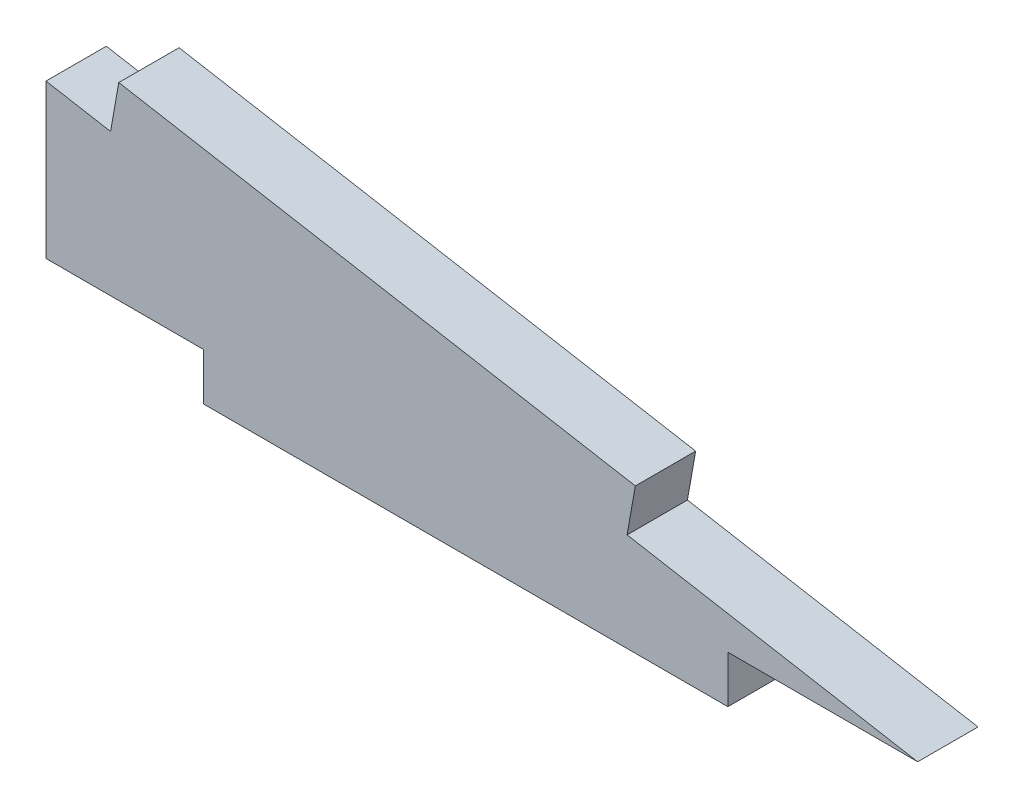
SolidWorks part; units mm, degrees
ref_plane "前视基准面" through (0, 0, 0) normal (0, 0, 1) x (1, 0, 0)
ref_plane "上视基准面" through (0, 0, 0) normal (0, 1, 0) x (1, 0, 0)
ref_plane "右视基准面" through (0, 0, 0) normal (1, 0, 0) x (0, 0, -1)
other "Configuration Table"
sketch "草图1" plane through (0, 0, 0) normal (0, 0, 1) x (1, 0, 0)
  line L2 (-22.3823, 3.7158) -> (-22.3823, 7.3158)
  line L3 (17.6177, 3.7158) -> (17.6177, 7.3158)
  line L4 (-22.3823, 7.3158) -> (-34.3823, 7.3158)
  line L5 (17.6177, 7.3158) -> (24.855, 7.3158)
  line L6 (-34.3823, 7.3158) -> (-34.3823, 19.037)
  line L7 (-34.3823, 19.037) -> (-29.4582, 18.1688)
  line L10 (-29.4582, 18.1688) -> (-28.8331, 21.7141)
  line L11 (-28.8331, 21.7141) -> (10.5592, 14.7681)
  line L12 (10.5592, 14.7681) -> (9.9341, 11.2228)
  line L15 (-22.3823, 3.7158) -> (17.6177, 3.7158)
  line L16 (21.0132, 9.2693) -> (9.9341, 11.2228)
  line L17 (21.0132, 9.2693) -> (32.0922, 7.3158)
  line L18 (24.855, 7.3158) -> (32.0922, 7.3158)
  point P4 (0, 0)
  dimension "D1" = 40
  dimension "D2" = 3.6
  dimension "D3" = 12
  dimension "D4" = 3.6
  dimension "D5" = 40
  dimension "D6" = 3.6
  dimension "D7" = 3.6
  dimension "D8" = 22.5
  dimension "D9" = 90
  dimension "D10" = 90
  dimension "D11" = 90
  dimension "D12" = 90
  dimension "D13" = 90
  dimension "D14" = 90
  dimension "D15" = 10
  dimension "D16" = 10
  dimension "D17" = 90
  dimension "D18" = 90
  dimension "D19" = 5
  dimension "D20" = 90
  dimension "D21" = 90
  dimension "D22" = 10
  dimension "D23" = 14.4745
extrude "凸台-拉伸1" add sketch "草图1" along normal blind 4.6
